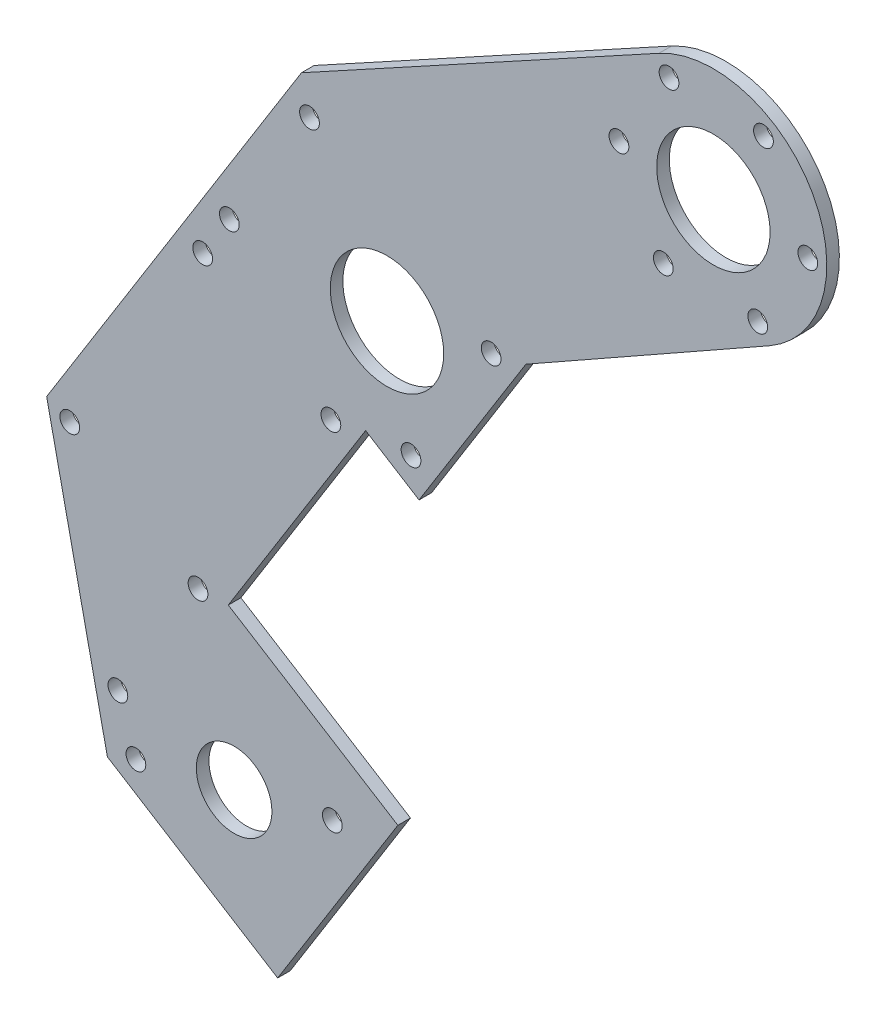
SolidWorks part; units mm, degrees
ref_plane "Front Plane" through (0, 0, 0) normal (0, 0, 1) x (1, 0, 0)
ref_plane "Top Plane" through (0, 0, 0) normal (0, 1, 0) x (1, 0, 0)
ref_plane "Right Plane" through (0, 0, 0) normal (1, 0, 0) x (0, 0, -1)
sketch "Sketch1" plane through (0, 0, -14.1946) normal (0, 0, 1) x (1, 0, 0)
  line L0 (-11.4036, 461.0409) -> (18.8813, 509.5069)
  line L1 (-54.3079, 487.8505) -> (-69.6155, 558.824)
  line L2 (18.8813, 509.5069) -> (-23.8465, 536.2061)
  line L4 (-11.4036, 461.0409) -> (-54.3079, 487.8505)
  line L5 (-69.6155, 558.824) -> (-5.4017, 661.5875)
  line L6 (-23.8465, 536.2061) -> (10.7592, 591.5868)
  line L10 (51.1419, 626.2552) -> (112.462, 660.9373)
  line L11 (10.7592, 591.5868) -> (24.222, 583.1743)
  line L13 (24.222, 583.1743) -> (51.1419, 626.2552)
  line L16 (-5.4017, 661.5875) -> (84.678, 710.8773)
  circle A2 centre (16.1415, 618.1747) radius 14.2875
  circle A3 centre (-22.3737, 496.6228) radius 9.525
  circle A5 centre (98.3945, 685.8096) radius 14.2875
  arc A7 (112.462, 660.9373) -> (84.678, 710.8773) centre (98.3945, 685.8096) ccw
  circle A8 centre (16.1415, 618.1747) radius 127.508 construction
  point P5 (-22.3737, 496.6228)
  point P12 (-22.3737, 496.6228)
  point P33 (98.3945, 685.8096)
extrude "Boss-Extrude1" add sketch "Sketch1" along normal blind 3.175
sketch "Sketch17" plane through (0, 0, -11.0196) normal (0, 0, 1) x (1, 0, 0)
  line L0 (-47.1227, 490.909) -> (-22.3737, 496.6228)
  line L1 (-22.3737, 496.6228) -> (2.3753, 502.3365)
  line L2 (16.1415, 618.1747) -> (37.6819, 604.7147) construction
  line L12 (24.222, 583.1743) -> (51.1419, 626.2552) construction
  line L13 (37.6819, 604.7147) -> (27.587, 588.5594) construction
  line L14 (27.587, 588.5594) -> (22.2019, 591.9244) construction
  line L15 (22.2019, 591.9244) -> (-28.9566, 623.8918) construction
  line L16 (-5.4017, 661.5875) -> (-69.6155, 558.824) construction
  line L17 (-28.9566, 623.8918) -> (-23.5715, 620.5268) construction
  line L18 (-23.5715, 620.5268) -> (-3.3816, 652.8374) construction
  line L19 (-3.3816, 652.8374) -> (42.3918, 624.2351) construction
  line L20 (10.7592, 591.5868) -> (5.3741, 594.9518) construction
  line L21 (5.3741, 594.9518) -> (-31.4748, 535.9811) construction
  line L22 (-31.4748, 535.9811) -> (-51.6648, 503.6705) construction
  line L23 (5.3741, 594.9518) -> (2.0091, 589.5667) construction
  line L24 (-31.4748, 535.9811) -> (-63.7855, 556.1711) construction
  line L25 (2.0091, 589.5667) -> (-30.3015, 609.7566) construction
  circle A0 centre (-22.3737, 496.6228) radius 25.4
  dimension "D1" = 50.8
hole_wizard "#10 Clearance Hole2" positions "Sketch20" profile "Sketch21" hole size "#10" standard "ANSI Inch" end condition through all
sketch "Sketch20" plane through (0, 0, -11.0196) normal (0, 0, 1) x (1, 0, 0)
  point P0 (2.3753, 502.3365)
  point P3 (-47.1227, 490.909)
  point P24 (-3.3816, 652.8374)
  point P27 (42.3918, 624.2351)
  point P30 (22.2019, 591.9244)
  point P33 (-23.5715, 620.5268)
  point P42 (-31.4748, 535.9811)
  point P45 (-63.7855, 556.1711)
  point P48 (-51.6648, 503.6705)
  point P54 (2.0091, 589.5667)
  point P57 (-30.3015, 609.7566)
sketch "Sketch21" plane through (2.3753, 502.3365, -11.0196) normal (1, 0, 0) x (0, -1, 0)
  line L0 (0, 0) -> (0, 3.175)
  line L1 (0, 3.175) -> (2.4892, 3.175)
  line L2 (2.4892, 3.175) -> (2.4892, 0)
  line L5 (2.4892, 0) -> (0, 0)
  line L11 (0, -6.35) -> (0, 107.95) construction
  dimension "Thru Hole Dia." = 4.9784
  dimension "Thru Hole Depth" = 3.175
sketch "Sketch22" plane through (0, 0, -11.0196) normal (0, 0, 1) x (1, 0, 0)
  line L0 (98.3945, 685.8096) -> (111.0132, 706.0038) construction
  line L2 (111.0132, 706.0038) -> (87.2152, 706.8348) construction
  line L3 (87.2152, 706.8348) -> (74.5965, 686.6407) construction
  line L4 (74.5965, 686.6407) -> (85.7758, 665.6155) construction
  line L5 (85.7758, 665.6155) -> (109.5738, 664.7845) construction
  line L6 (109.5738, 664.7845) -> (122.1925, 684.9786) construction
  line L7 (122.1925, 684.9786) -> (111.0132, 706.0038) construction
  circle A0 centre (98.3945, 685.8096) radius 23.8125 construction
hole_wizard "#10 Clearance Hole3" positions "Sketch23" profile "Sketch24" hole size "#10" standard "ANSI Inch" end condition through all
sketch "Sketch23" plane through (0, 0, -11.0196) normal (0, 0, 1) x (1, 0, 0)
  point P0 (111.0132, 706.0038)
  point P3 (122.1925, 684.9786)
  point P6 (109.5738, 664.7845)
  point P9 (85.7758, 665.6155)
  point P12 (74.5965, 686.6407)
  point P15 (87.2152, 706.8348)
sketch "Sketch24" plane through (111.0132, 706.0038, -11.0196) normal (1, 0, 0) x (0, -1, 0)
  line L0 (0, 0) -> (0, 3.175)
  line L1 (0, 3.175) -> (2.4892, 3.175)
  line L2 (2.4892, 3.175) -> (2.4892, 0)
  line L5 (2.4892, 0) -> (0, 0)
  line L11 (0, -6.35) -> (0, 107.95) construction
  dimension "Thru Hole Dia." = 4.9784
  dimension "Thru Hole Depth" = 3.175
